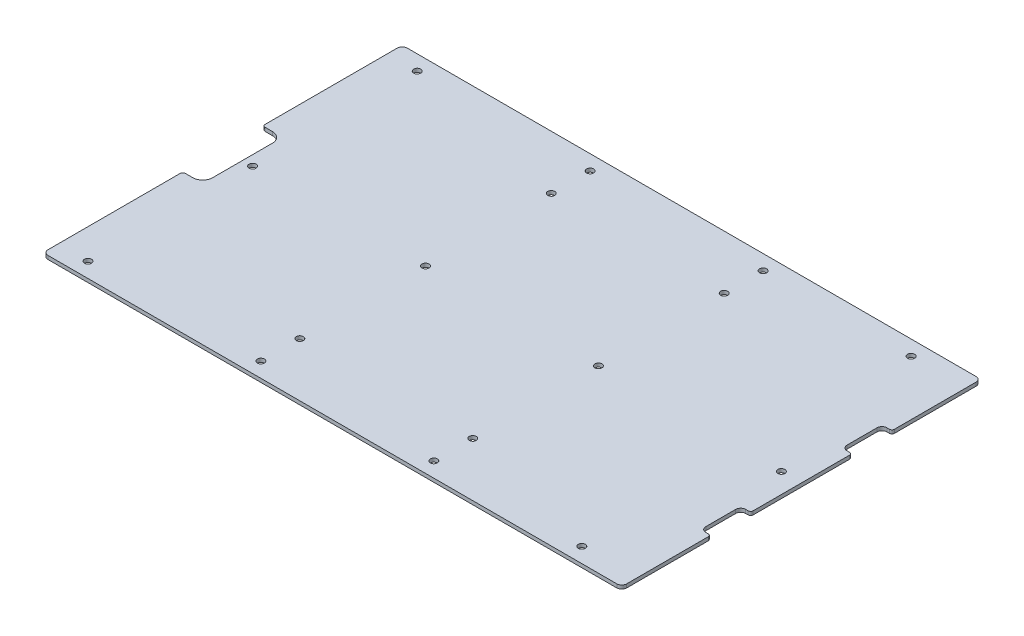
SolidWorks part; units mm, degrees
material "1060 Alloy"
ref_plane "Front" through (0, 0, 0) normal (0, 0, 1) x (1, 0, 0)
ref_plane "Top" through (0, 0, 0) normal (0, 1, 0) x (1, 0, 0)
ref_plane "Right" through (0, 0, 0) normal (1, 0, 0) x (0, 0, -1)
sketch "Sketch1" plane through (0, 0, 0) normal (0, 1, 0) x (1, 0, 0)
  line L0 (-55.0333, 0) -> (-165.1, 0) construction
  line L1 (-180.975, 114.3) -> (180.975, 114.3)
  line L2 (-184.15, 111.125) -> (-184.15, -111.125)
  line L3 (-180.975, -114.3) -> (180.975, -114.3)
  line L4 (184.15, 111.125) -> (184.15, -111.125)
  line L5 (-184.15, 114.3) -> (184.15, -114.3) construction
  line L6 (-184.15, -114.3) -> (184.15, 114.3) construction
  line L7 (-165.1, -104.775) -> (165.1, -104.775) construction
  line L8 (-165.1, -104.775) -> (-165.1, 104.775) construction
  line L9 (-165.1, 104.775) -> (165.1, 104.775) construction
  line L10 (165.1, -104.775) -> (165.1, 104.775) construction
  line L11 (-165.1, -104.775) -> (165.1, 104.775) construction
  line L12 (-165.1, 104.775) -> (165.1, -104.775) construction
  line L13 (-55.0333, -104.775) -> (55.0333, -104.775) construction
  line L14 (-55.0333, -104.775) -> (-55.0333, 104.775) construction
  line L15 (-55.0333, 104.775) -> (55.0333, 104.775) construction
  line L16 (55.0333, -104.775) -> (55.0333, 104.775) construction
  line L17 (-55.0333, -104.775) -> (55.0333, 104.775) construction
  line L18 (-55.0333, 104.775) -> (55.0333, -104.775) construction
  line L19 (55.0333, 0) -> (165.1, 0) construction
  line L20 (-55.0333, 0) -> (55.0333, 0) construction
  line L31 (-55.0291, 80.01) -> (55.0291, 80.01) construction
  line L32 (149.225, -104.775) -> (149.225, 104.775) construction
  line L33 (-55.0291, 80.01) -> (-55.0291, -80.01) construction
  line L34 (-55.0291, -80.01) -> (55.0291, -80.01) construction
  line L35 (55.0291, 80.01) -> (55.0291, -80.01) construction
  line L36 (-55.0291, 80.01) -> (55.0291, -80.01) construction
  line L37 (-55.0291, -80.01) -> (55.0291, 80.01) construction
  circle A0 centre (-165.1, 104.775) radius 2.2479
  circle A1 centre (-55.0333, 104.775) radius 2.2479
  circle A2 centre (55.0333, 104.775) radius 2.2479
  circle A3 centre (165.1, 104.775) radius 2.2479 construction
  circle A4 centre (165.1, -104.775) radius 2.2479 construction
  circle A5 centre (55.0333, -104.775) radius 2.2479
  circle A6 centre (-55.0333, -104.775) radius 2.2479
  circle A7 centre (-165.1, -104.775) radius 2.2479
  circle A12 centre (-55.0333, 0) radius 2.2479
  circle A13 centre (55.0333, 0) radius 2.2479
  arc A14 (184.15, 111.125) -> (180.975, 114.3) centre (180.975, 111.125) ccw
  arc A15 (184.15, -111.125) -> (180.975, -114.3) centre (180.975, -111.125) cw
  arc A16 (-180.975, -114.3) -> (-184.15, -111.125) centre (-180.975, -111.125) cw
  arc A17 (-180.975, 114.3) -> (-184.15, 111.125) centre (-180.975, 111.125) ccw
  circle A24 centre (149.225, -104.775) radius 2.2479
  circle A25 centre (149.225, 104.775) radius 2.2479
  circle A26 centre (55.0291, -80.01) radius 2.2479
  circle A27 centre (-55.0291, -80.01) radius 2.2479
  circle A28 centre (-55.0291, 80.01) radius 2.2479
  circle A29 centre (55.0291, 80.01) radius 2.2479
  circle A30 centre (171.45, 0) radius 2.2479
  circle A31 centre (-165.1, 0) radius 2.2479
  point P0 (0, 0)
  point P6 (0, 0)
  point P11 (0, 0)
  point P28 (0, 0)
  point P29 (0, 0)
  point P32 (0, 0)
  dimension "D5" = 4.4958
  dimension "D8" = 4.4958
  dimension "D11" = 3.175
  dimension "D10" = 12.7
  dimension "D12" = 19.05
  dimension "D13" = 110.0667
  dimension "D1" = 368.3
  dimension "D2" = 228.6
  dimension "D3" = 9.525
  dimension "D4" = 19.05
  dimension "D6" = 160.02
  dimension "D7" = 34.925
  dimension "D9" = 110.0582
extrude "Boss-Extrude1" add sketch "Sketch1" along normal blind 2.286
sketch "Sketch2" plane through (0, 0, 0) normal (0, -1, 0) x (1, 0, 0)
  line L5 (184.15, 111.125) -> (184.15, -111.125) construction
  line L6 (184.15, 57.658) -> (180.975, 57.658)
  line L7 (184.15, 57.658) -> (184.15, 32.258)
  line L8 (184.15, 32.258) -> (180.975, 32.258)
  line L9 (177.8, 54.483) -> (177.8, 35.433)
  line L10 (-184.15, 0) -> (185.7248, 0) construction
  line L11 (-184.15, -111.125) -> (-184.15, 111.125) construction
  line L12 (185.7248, -116.6368) -> (185.7248, 116.6368) construction
  line L13 (177.8, 44.958) -> (184.15, 44.958) construction
  line L14 (184.15, -32.258) -> (180.975, -32.258)
  line L15 (184.15, -57.658) -> (184.15, -32.258)
  line L16 (177.8, -54.483) -> (177.8, -35.433)
  line L17 (184.15, -57.658) -> (180.975, -57.658)
  line L19 (-184.15, 25.4) -> (-177.8, 25.4)
  line L20 (-184.15, 25.4) -> (-184.15, -25.4)
  line L21 (-184.15, -25.4) -> (-177.8, -25.4)
  line L22 (-171.45, 19.05) -> (-171.45, -19.05)
  arc A0 (180.975, -57.658) -> (177.8, -54.483) centre (180.975, -54.483) cw
  arc A1 (177.8, -35.433) -> (180.975, -32.258) centre (180.975, -35.433) cw
  arc A2 (177.8, 35.433) -> (180.975, 32.258) centre (180.975, 35.433) ccw
  arc A3 (177.8, 54.483) -> (180.975, 57.658) centre (180.975, 54.483) cw
  arc A4 (-171.45, -19.05) -> (-177.8, -25.4) centre (-177.8, -19.05) cw
  arc A5 (-171.45, 19.05) -> (-177.8, 25.4) centre (-177.8, 19.05) ccw
  point P20 (177.8, -57.658)
  point P23 (177.8, -32.258)
  point P26 (177.8, 32.258)
  point P29 (177.8, 57.658)
  point P38 (-171.45, 25.4)
  dimension "D4" = 3.175
  dimension "D7" = 6.35
  dimension "D1" = 25.4
  dimension "D2" = 44.958
  dimension "D3" = 6.35
  dimension "D5" = 50.8
  dimension "D6" = 12.7
extrude "Cut-Extrude1" cut sketch "Sketch2" against normal through all
fillet "Fillet1" radius 1.5875 6 edges at (184.15, 1.143, -57.658) (184.15, 1.143, -32.258) (184.15, 1.143, 32.258) (184.15, 1.143, 57.658) (-184.15, 1.143, -25.4) (-184.15, 1.143, 25.4)
sketch "Sketch3" plane through (0, 2.286, 0) normal (0, 1, 0) x (1, 0, 0)
  line L0 (-198.0256, -111.0509) -> (-198.0256, 117.5491)
  line L1 (204.2781, -126.2696) -> (-1014.9219, -126.2696)
  line L2 (204.2781, -126.2696) -> (204.2781, 1092.9304)
  line L3 (204.2781, 1092.9304) -> (-1014.9219, 1092.9304)
  line L4 (-1014.9219, -126.2696) -> (-1014.9219, 1092.9304)
  line L5 (182.9744, -111.0509) -> (-185.3256, -111.0509)
  line L6 (182.9744, -111.0509) -> (182.9744, 117.5491)
  line L7 (182.9744, 117.5491) -> (-185.3256, 117.5491)
  line L8 (-185.3256, -111.0509) -> (-185.3256, 117.5491)
  line L9 (-198.0256, -111.0509) -> (-566.3256, -111.0509)
  line L10 (-566.3256, -111.0509) -> (-566.3256, 117.5491)
  line L11 (-198.0256, 117.5491) -> (-566.3256, 117.5491)
  line L12 (-579.0256, -111.0509) -> (-579.0256, 117.5491)
  line L13 (-579.0256, -111.0509) -> (-947.3256, -111.0509)
  line L14 (-947.3256, -111.0509) -> (-947.3256, 117.5491)
  line L15 (-579.0256, 117.5491) -> (-947.3256, 117.5491)
  line L16 (-198.0256, 130.2491) -> (-198.0256, 358.8491)
  line L17 (-198.0256, 130.2491) -> (-566.3256, 130.2491)
  line L18 (-566.3256, 130.2491) -> (-566.3256, 358.8491)
  line L19 (-198.0256, 358.8491) -> (-566.3256, 358.8491)
  line L20 (-579.0256, 130.2491) -> (-579.0256, 358.8491)
  line L21 (-579.0256, 130.2491) -> (-947.3256, 130.2491)
  line L22 (-947.3256, 130.2491) -> (-947.3256, 358.8491)
  line L23 (-579.0256, 358.8491) -> (-947.3256, 358.8491)
  line L24 (-198.0256, 371.5491) -> (-198.0256, 600.1491)
  line L25 (-198.0256, 371.5491) -> (-566.3256, 371.5491)
  line L26 (-566.3256, 371.5491) -> (-566.3256, 600.1491)
  line L27 (-198.0256, 600.1491) -> (-566.3256, 600.1491)
  line L28 (-579.0256, 371.5491) -> (-579.0256, 600.1491)
  line L29 (-579.0256, 371.5491) -> (-947.3256, 371.5491)
  line L30 (-947.3256, 371.5491) -> (-947.3256, 600.1491)
  line L31 (-579.0256, 600.1491) -> (-947.3256, 600.1491)
  line L32 (-198.0256, 612.8491) -> (-198.0256, 841.4491)
  line L33 (-198.0256, 612.8491) -> (-566.3256, 612.8491)
  line L34 (-566.3256, 612.8491) -> (-566.3256, 841.4491)
  line L35 (-198.0256, 841.4491) -> (-566.3256, 841.4491)
  line L36 (-579.0256, 612.8491) -> (-579.0256, 841.4491)
  line L37 (-579.0256, 612.8491) -> (-947.3256, 612.8491)
  line L38 (-947.3256, 612.8491) -> (-947.3256, 841.4491)
  line L39 (-579.0256, 841.4491) -> (-947.3256, 841.4491)
  line L40 (-198.0256, 854.1491) -> (-198.0256, 1082.7491)
  line L41 (-198.0256, 854.1491) -> (-566.3256, 854.1491)
  line L42 (-566.3256, 854.1491) -> (-566.3256, 1082.7491)
  line L43 (-198.0256, 1082.7491) -> (-566.3256, 1082.7491)
  line L44 (-579.0256, 854.1491) -> (-579.0256, 1082.7491)
  line L45 (-579.0256, 854.1491) -> (-947.3256, 854.1491)
  line L46 (-947.3256, 854.1491) -> (-947.3256, 1082.7491)
  line L47 (-579.0256, 1082.7491) -> (-947.3256, 1082.7491)
  line L48 (182.9744, 130.2491) -> (182.9744, 358.8491)
  line L49 (182.9744, 130.2491) -> (-185.3256, 130.2491)
  line L50 (-185.3256, 130.2491) -> (-185.3256, 358.8491)
  line L51 (182.9744, 358.8491) -> (-185.3256, 358.8491)
  line L52 (182.9744, 371.5491) -> (182.9744, 600.1491)
  line L53 (182.9744, 371.5491) -> (-185.3256, 371.5491)
  line L54 (-185.3256, 371.5491) -> (-185.3256, 600.1491)
  line L55 (182.9744, 600.1491) -> (-185.3256, 600.1491)
  line L56 (182.9744, 612.8491) -> (182.9744, 841.4491)
  line L57 (182.9744, 612.8491) -> (-185.3256, 612.8491)
  line L58 (-185.3256, 612.8491) -> (-185.3256, 841.4491)
  line L59 (182.9744, 841.4491) -> (-185.3256, 841.4491)
  line L60 (182.9744, 854.1491) -> (182.9744, 1082.7491)
  line L61 (182.9744, 854.1491) -> (-185.3256, 854.1491)
  line L62 (-185.3256, 854.1491) -> (-185.3256, 1082.7491)
  line L63 (182.9744, 1082.7491) -> (-185.3256, 1082.7491)
  dimension "D1" = 1219.2
  dimension "D2" = 1219.2
  dimension "D3" = 368.3
  dimension "D4" = 228.6
  dimension "D5" = 3
  dimension "D6" = 5
